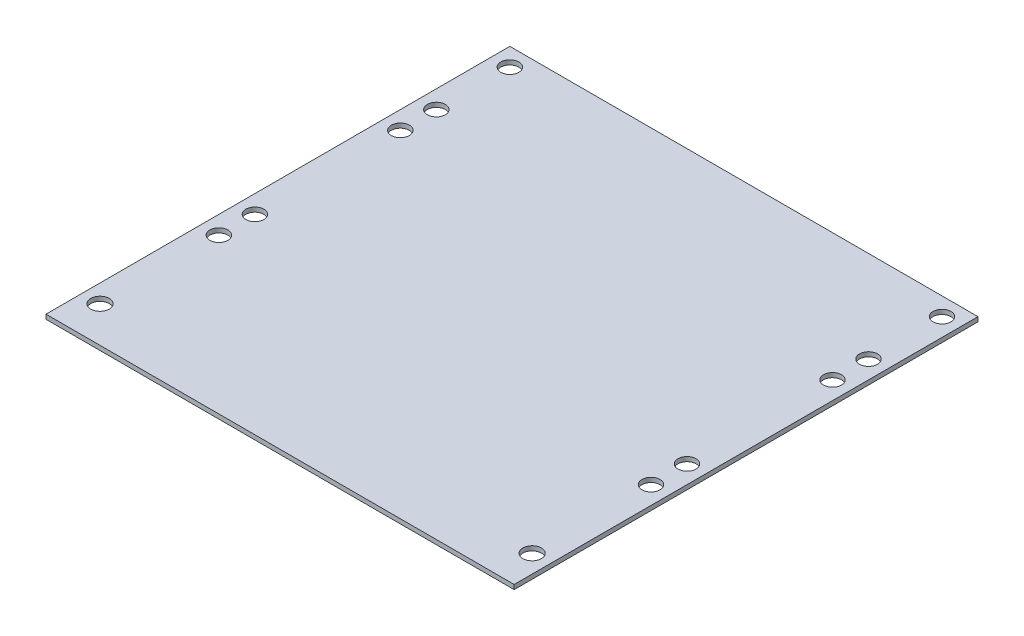
SolidWorks part; units mm, degrees
material "PE High Density"
ref_plane "Front Plane" through (0, 0, 0) normal (0, 0, 1) x (1, 0, 0)
ref_plane "Top Plane" through (0, 0, 0) normal (0, 1, 0) x (1, 0, 0)
ref_plane "Right Plane" through (0, 0, 0) normal (1, 0, 0) x (0, 0, -1)
sketch "Sketch1" plane through (0, 0, 0) normal (0, 1, 0) x (1, 0, 0)
  line L0 (6.35, 12.7) -> (6.35, 60.96) construction
  line L1 (0, 0) -> (165.1, 0)
  line L2 (0, 0) -> (0, 163.576)
  line L3 (0, 163.576) -> (165.1, 163.576)
  line L4 (165.1, 0) -> (165.1, 163.576)
  line L5 (6.35, 60.96) -> (6.35, 67.31) construction
  line L6 (6.35, 60.96) -> (6.35, 124.968) construction
  line L7 (6.35, 124.968) -> (6.35, 131.318) construction
  line L8 (6.35, 124.968) -> (6.35, 163.576) construction
  line L9 (82.55, 163.576) -> (82.55, 107.4456) construction
  circle A0 centre (6.35, 12.7) radius 3.2639
  circle A2 centre (6.35, 54.61) radius 3.175
  circle A3 centre (6.35, 67.31) radius 3.175
  circle A4 centre (6.35, 118.618) radius 3.175
  circle A5 centre (6.35, 131.318) radius 3.175
  circle A6 centre (6.35, 157.226) radius 3.175
  circle A7 centre (158.75, 12.7) radius 3.2639
  circle A8 centre (158.75, 54.61) radius 3.175
  circle A9 centre (158.75, 67.31) radius 3.175
  circle A10 centre (158.75, 118.618) radius 3.175
  circle A11 centre (158.75, 131.318) radius 3.175
  circle A12 centre (158.75, 157.226) radius 3.175
  dimension "D2" = 6.35
  dimension "D3" = 48.26
  dimension "D4" = 6.5278
  dimension "D6" = 12.7
  dimension "D5" = 6.35
  dimension "D7" = 6.35
  dimension "D8" = 6.35
  dimension "D9" = 6.35
  dimension "D11" = 6.35
  dimension "D12" = 6.35
  dimension "D14" = 6.35
  dimension "D16" = 6.35
  dimension "D17" = 6.35
  dimension "D1" = 165.1
  dimension "D10" = 64.008
  dimension "D13" = 6.35
  dimension "D15" = 38.608
extrude "Boss-Extrude1" add sketch "Sketch1" along normal blind 1.5875
